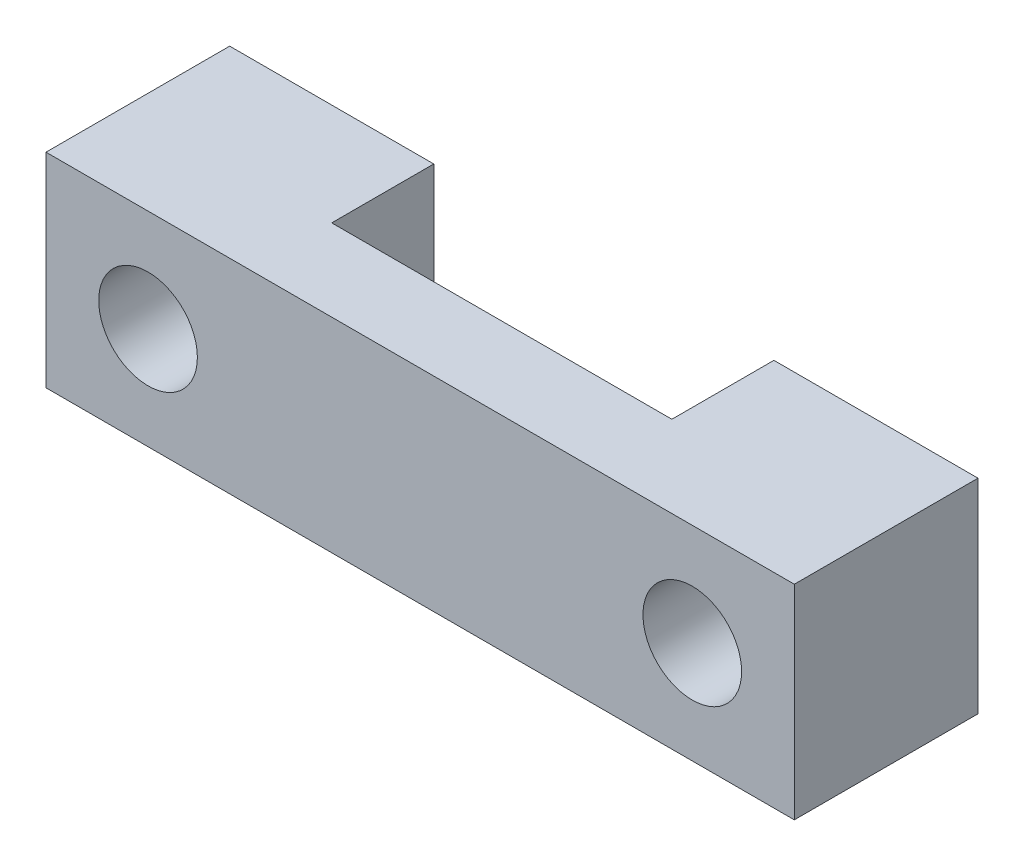
SolidWorks part; units mm, degrees
ref_plane "Front Plane" through (0, 0, 0) normal (0, 0, 1) x (1, 0, 0)
ref_plane "Top Plane" through (0, 0, 0) normal (0, 1, 0) x (1, 0, 0)
ref_plane "Right Plane" through (0, 0, 0) normal (1, 0, 0) x (0, 0, -1)
sketch "Sketch1" plane through (0, 0, 0) normal (0, 0, 1) x (1, 0, 0)
  line L1 (-13.97, -3.81) -> (13.97, -3.81)
  line L2 (-13.97, -3.81) -> (-13.97, 3.81)
  line L3 (-13.97, 3.81) -> (13.97, 3.81)
  line L4 (13.97, -3.81) -> (13.97, 3.81)
  line L5 (-13.97, -3.81) -> (13.97, 3.81) construction
  line L6 (-13.97, 3.81) -> (13.97, -3.81) construction
  circle A0 centre (-10.16, 0) radius 1.8415
  circle A1 centre (10.16, 0) radius 1.8415
  point P0 (0, 0)
  point P10 (0, 0)
  point P11 (0, 0)
  dimension "D3" = 3.683
  dimension "D1" = 7.62
  dimension "D2" = 27.94
  dimension "D4" = 3.81
  dimension "D5" = 3.81
extrude "Boss-Extrude1" add sketch "Sketch1" along normal blind 6.858
sketch "Sketch2" plane through (0, 3.81, 0) normal (0, 1, 0) x (1, 0, 0)
  line L0 (13.97, 0) -> (-13.97, 0) construction
  line L1 (-6.35, 0) -> (6.35, 0)
  line L2 (-6.35, 0) -> (-6.35, -3.81)
  line L3 (-6.35, -3.81) -> (6.35, -3.81)
  line L4 (6.35, 0) -> (6.35, -3.81)
  line L5 (-13.97, -6.858) -> (-13.97, 0) construction
  line L6 (13.97, -6.858) -> (13.97, 0) construction
  dimension "D1" = 7.62
  dimension "D2" = 7.62
  dimension "D3" = 3.81
extrude "Cut-Extrude1" cut sketch "Sketch2" against normal through all
